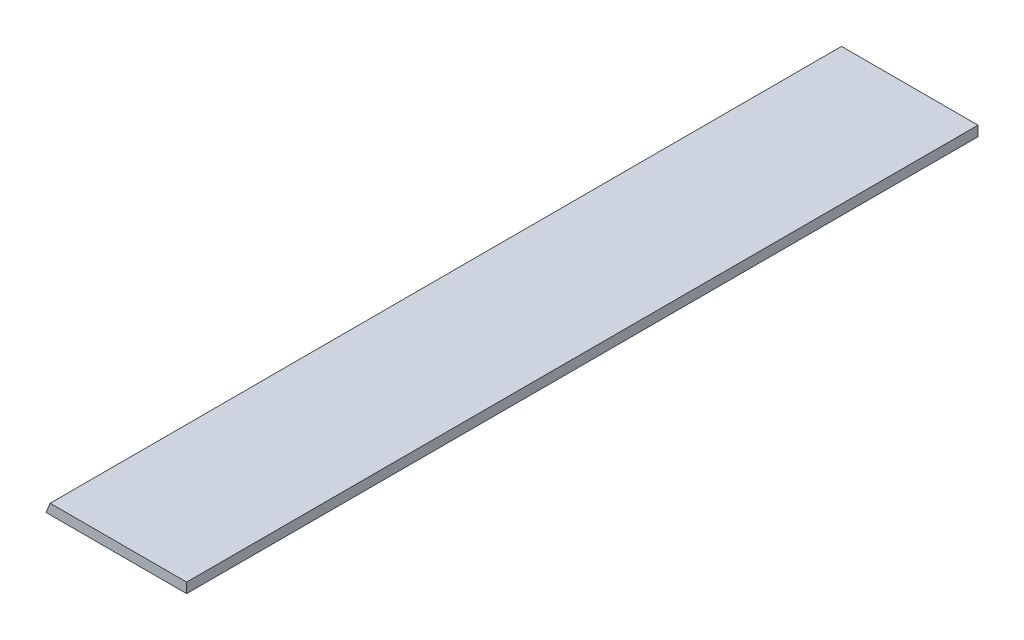
SolidWorks part; units mm, degrees
ref_plane "Front Plane" through (0, 0, 0) normal (0, 0, 1) x (1, 0, 0)
ref_plane "Top Plane" through (0, 0, 0) normal (0, 1, 0) x (1, 0, 0)
ref_plane "Right Plane" through (0, 0, 0) normal (1, 0, 0) x (0, 0, -1)
sketch "Sketch1" plane through (0, 0, 0) normal (0, 0, 1) x (1, 0, 0)
  line L0 (0, 0) -> (2.6303, 6.35)
  line L1 (2.6303, 6.35) -> (89.154, 6.35)
  line L2 (89.154, 6.35) -> (89.154, 0)
  line L3 (89.154, 0) -> (0, 0)
  dimension "D1" = 89.154
  dimension "D2" = 67.5
  dimension "D3" = 6.35
extrude "Boss-Extrude1" add sketch "Sketch1" along normal blind 501.65
